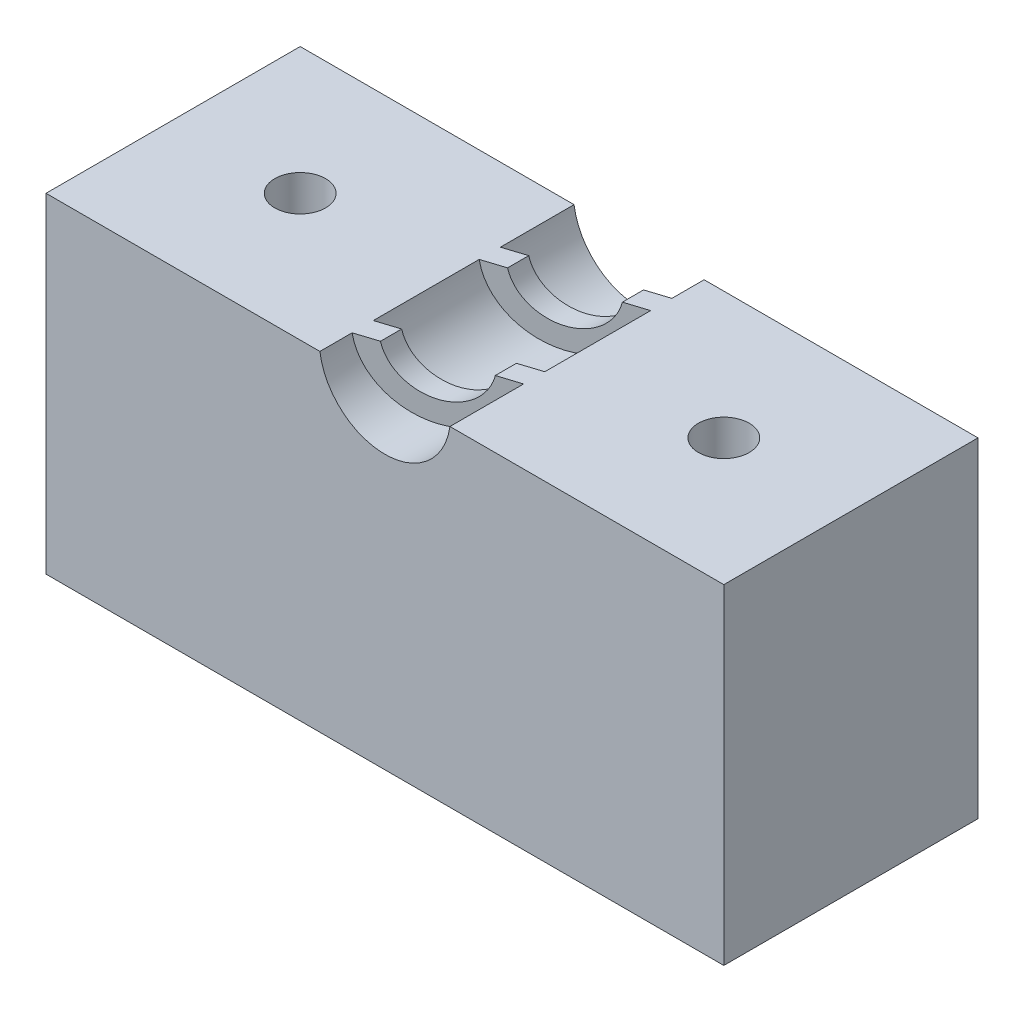
SolidWorks part; units mm, degrees
ref_plane "前视基准面" through (0, 0, 0) normal (0, 0, 1) x (1, 0, 0)
ref_plane "上视基准面" through (0, 0, 0) normal (0, 1, 0) x (1, 0, 0)
ref_plane "右视基准面" through (0, 0, 0) normal (1, 0, 0) x (0, 0, -1)
other "Configuration Table"
sketch "草图1" plane through (0, 0, 0) normal (0, 0, 1) x (1, 0, 0)
  line L1 (-8, -8) -> (8, -8)
  line L2 (-8, -8) -> (-8, 8)
  line L3 (-8, 8) -> (8, 8)
  line L4 (8, -8) -> (8, 8)
  line L5 (-8, -8) -> (8, 8) construction
  line L6 (-8, 8) -> (8, -8) construction
  circle A0 centre (0, 0) radius 1.55
  point P0 (0, 0)
  dimension "D3" = 3.1
  dimension "D1" = 16
  dimension "D2" = 16
extrude "凸台-拉伸1" add sketch "草图1" along normal mid plane 6
sketch "草图6" plane through (0, 0, 0) normal (0, 1, 0) x (1, 0, 0)
  line L0 (-1.55, -3) -> (1.55, -3) construction
  line L1 (1.55, 3) -> (-1.55, 3) construction
  line L2 (-1.55, -3) -> (1.55, -3)
  line L3 (1.55, 3) -> (-1.55, 3)
  line L4 (-1.55, 3) -> (-1.55, -3)
  line L5 (1.55, -3) -> (1.55, 3)
  line L6 (-1.55, 0.7565) -> (1.55, 1.7435)
  line L7 (1.55, 1.7435) -> (1.55, 2.2435)
  line L8 (1.55, 2.2435) -> (-1.55, 1.2565)
  line L9 (-1.55, -1.7435) -> (1.55, -0.7565)
  line L10 (-1.55, -2.2435) -> (1.55, -1.2565)
  line L11 (-2.0945, -0.6668) -> (3.135, 0.9981) construction
  line L12 (-3.1004, 0) -> (4.2723, 0) construction
  dimension "D1" = 2.5
  dimension "D2" = 0.5
  dimension "D3" = 0.5
  dimension "D4" = 17.66
extrude "凸台-拉伸2" add sketch "草图6" against normal up to surface (8 mm away) contours L4 L10 L5 L9 | L5 L8 L4 L6 region at (0, 0, 1.5) region at (0, 0, -1.5) up to face at (0, -8, 0)
sketch "草图7" plane through (0, 0, 0) normal (0, 0, 1) x (1, 0, 0)
  line L0 (0, 0) -> (-1.0279, -0.2141)
  line L1 (0, 0) -> (1.0279, -0.2141)
  line L2 (-1.0279, -0.2141) -> (-8, -0.2141)
  line L3 (1.0279, -0.2141) -> (8, -0.2141)
  line L6 (8, -8) -> (8, 8)
  line L7 (-8, -8) -> (8, -8)
  line L8 (-8, 8) -> (-8, -8)
  line L9 (8, 8) -> (-8, 8)
  line L10 (8, -8) -> (8, 8)
  line L11 (-8, -8) -> (8, -8)
  line L12 (-8, 8) -> (-8, -8)
  line L13 (8, 8) -> (-8, 8)
  circle A0 centre (0, 0) radius 1.05
  dimension "D1" = 2.1
  dimension "D2" = 0
  dimension "D3" = 156.47
extrude "切除-拉伸2" cut sketch "草图7" against normal through all both and the other way through all contours A0 L3 L10 L13 L12 L2 | L1 A0 L0 | L0 A0 L1 region at (0, -0.5019, 0) region at (0, 0.3858, 0) region at (0, 3.953, 0)
sketch "草图8" plane through (0, 0, 0) normal (0, 1, 0) x (1, 0, 0)
  line L0 (0, 5.5834) -> (0, -5.0797) construction
  circle A0 centre (-5, 0) radius 0.6
  circle A1 centre (5, 0) radius 0.6
  dimension "D2" = 1.2
  dimension "D3" = 10
extrude "切除-拉伸3" cut sketch "草图8" against normal through all
sketch "草图9" plane through (0, -8, 0) normal (0, -1, 0) x (1, 0, 0)
  line L4 (-8, -3) -> (8, -3)
  line L5 (8, -3) -> (8, 3)
  line L6 (8, 3) -> (-8, 3)
  line L7 (-8, 3) -> (-8, -3)
  line L8 (-8, -3) -> (8, -3)
  line L9 (8, -3) -> (8, 3)
  line L10 (8, 3) -> (-8, 3)
  line L11 (-8, 3) -> (-8, -3)
  circle A0 centre (-5, 0) radius 0.6 construction
  circle A1 centre (5, 0) radius 0.6 construction
  circle A2 centre (-5, 0) radius 0.6
  circle A3 centre (5, 0) radius 0.6
  dimension "D1" = 0
extrude "凸台-拉伸3" [suppressed] add sketch "草图9" along normal offset from surface (0.455 mm away) 0.5
equation "\"x\"=0.8094"
